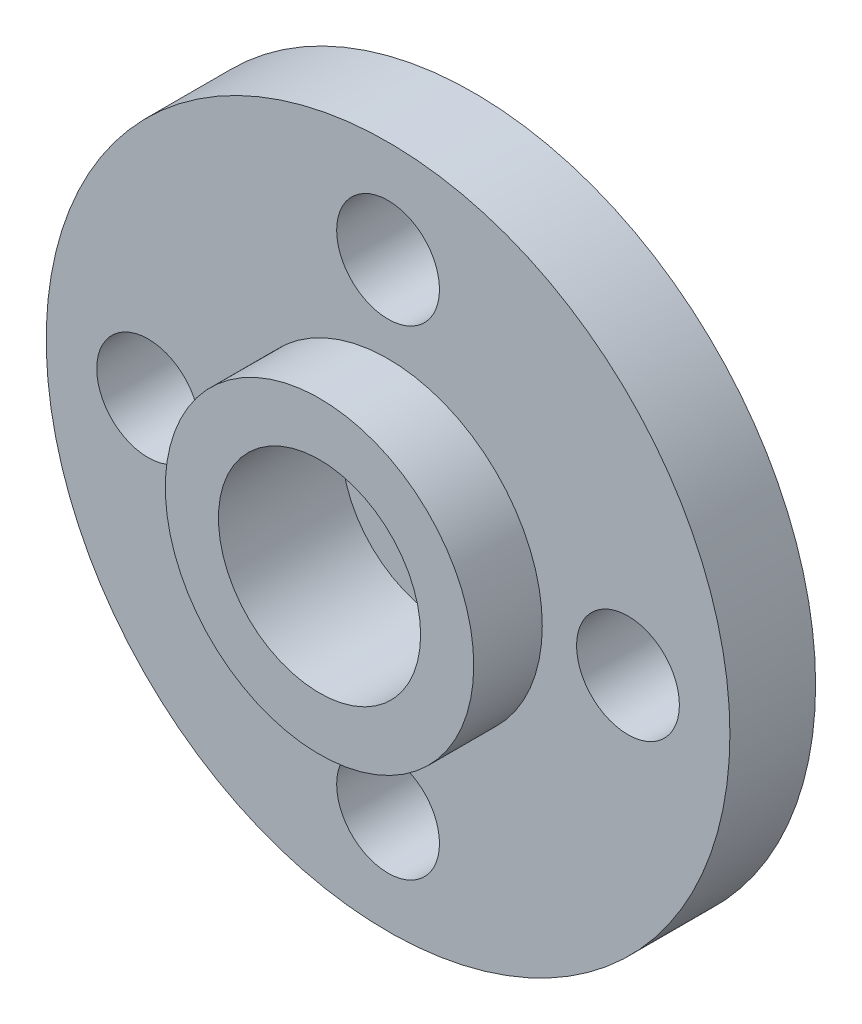
SolidWorks part; units mm, degrees
material "6061-T6 (SS)"
ref_plane "Front Plane" through (0, 0, 0) normal (0, 0, 1) x (1, 0, 0)
ref_plane "Top Plane" through (0, 0, 0) normal (0, 1, 0) x (1, 0, 0)
ref_plane "Right Plane" through (0, 0, 0) normal (1, 0, 0) x (0, 0, -1)
sketch "Sketch1" plane through (0, 0, 0) normal (0, 0, 1) x (1, 0, 0)
  circle A0 centre (0, 0) radius 2.95
  circle A1 centre (0, 0) radius 1.6
  circle A2 centre (0, 0) radius 4.5
  circle A3 centre (0, 0) radius 7 construction
  circle A4 centre (0, 0) radius 9.975
  point P6 (0, 7)
  point P8 (7, 0)
  point P9 (0, -7)
  point P10 (-7, 0)
  dimension "D1" = 3.2
  dimension "D2" = 5.9
  dimension "D3" = 9
  dimension "D4" = 14
  dimension "D5" = 19.95
sketch "Sketch4" plane through (0, 0, 0) normal (1, 0, 0) x (0, 0, -1)
  line L0 (0, 4.5) -> (-3.6, 4.5)
  line L1 (0, 4.5) -> (0, -4.5)
  line L2 (-3.6, 4.5) -> (-3.6, -4.5)
  line L3 (0, -4.5) -> (-3.6, -4.5)
  line L4 (0, 4.5) -> (0, -4.5) construction
  line L5 (-1.6, 9.975) -> (0.9, 9.975)
  line L6 (-1.6, 9.975) -> (-1.6, -9.975)
  line L7 (0.9, 9.975) -> (0.9, -9.975)
  line L8 (-1.6, -9.975) -> (0.9, -9.975)
  line L11 (0, 9.975) -> (0, -9.975) construction
  point P0 (0, 9.975)
  point P11 (0, 0)
  point P17 (0, -9.975)
  dimension "D1" = 3.6
  dimension "D2" = 4.5
  dimension "D3" = 2.5
extrude "Boss-Extrude2" add sketch "Sketch1" along normal up to vertex (3.6 mm away) from vertex contours A2 | A0 up to point (0, 4.5, 3.6) starting at point (0, 4.5, 0)
extrude "Boss-Extrude3" add sketch "Sketch1<4>" against normal up to vertex (0.9 mm away) from vertex contours A4 | A1 up to point (0, 9.975, -0.9) starting at point (0, 9.975, 1.6)
sketch "Sketch1<4>" plane through (0, 0, 0) normal (0, 0, 1) x (1, 0, 0) same geometry as "Sketch1"
extrude "Cut-Extrude1" cut sketch "Sketch1<6>" along normal up to vertex (3.6 mm away) from vertex contours A0 up to point (0, -4.5, 3.6) starting at point (0, -4.5, 0)
sketch "Sketch1<6>" plane through (0, 0, 0) normal (0, 0, 1) x (1, 0, 0) same geometry as "Sketch1"
sketch "Sketch7" plane through (0, 0, -0.9) normal (0, 0, -1) x (-1, 0, 0)
  point P0 (0, 7)
  point P3 (7, 0)
  point P6 (0, -7)
  point P9 (-7, 0)
hole_wizard "M3x0.5 Tapped Hole1" positions "Sketch7" profile "Sketch6" tap size "M3x0.5" standard "ANSI Metric" end condition up to next
sketch "Sketch6" plane through (0, 7, -0.9) normal (1, 0, 0) x (0, 1, 0)
  line L0 (0, 0) -> (0, 2.5)
  line L1 (0, 2.5) -> (1.5, 2.5)
  line L2 (1.5, 2.5) -> (1.5, 0)
  line L5 (1.5, 0) -> (0, 0)
  line L11 (0, -6.35) -> (0, 107.95) construction
  dimension "Thread Major Dia." = 3
  dimension "Thru Tap Drill Depth" = 2.5
